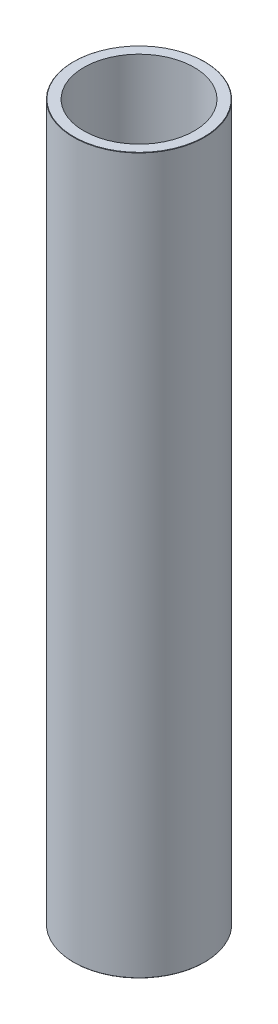
SolidWorks part; units mm, degrees
ref_plane "Front Plane" through (0, 0, 0) normal (0, 0, 1) x (1, 0, 0)
ref_plane "Top Plane" through (0, 0, 0) normal (0, 1, 0) x (1, 0, 0)
ref_plane "Right Plane" through (0, 0, 0) normal (1, 0, 0) x (0, 0, -1)
sketch "Sketch1" plane through (0, 0, 0) normal (0, 1, 0) x (1, 0, 0)
  circle A0 centre (0, 0) radius 55
  dimension "SHAFT_OD" = 110
extrude "Boss-Extrude1" add sketch "Sketch1" along normal blind 600
sketch "Sketch2" plane through (0, 0, 0) normal (0, 1, 0) x (1, 0, 0)
  circle A0 centre (0, 0) radius 46.2754
  dimension "BORE_D" = 92.5508
extrude "Cut-Extrude1" cut sketch "Sketch2" along normal through all
chamfer "Chamfer1" distance 0.2337 angle 52.809 2 edges at (0, 600, 55) (0, 0, 55) first distance on face at (0, 600, 55) first distance on face at (0, 0, 46.2754)
